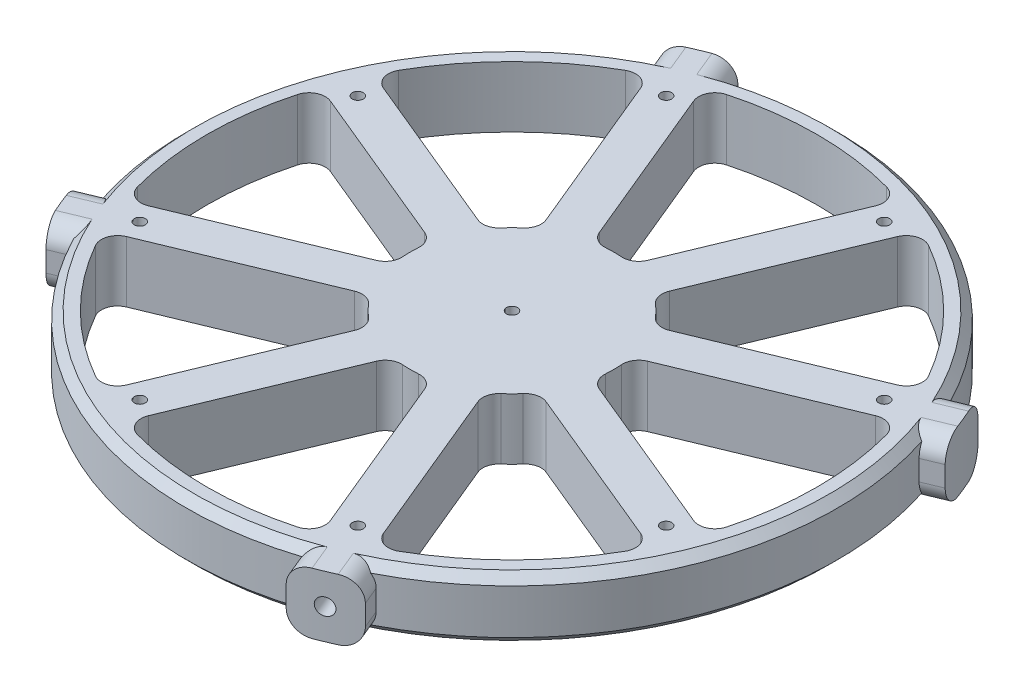
SolidWorks part; units mm, degrees
ref_plane "Front Plane" through (0, 0, 0) normal (0, 0, 1) x (1, 0, 0)
ref_plane "Top Plane" through (0, 0, 0) normal (0, 1, 0) x (1, 0, 0)
ref_plane "Right Plane" through (0, 0, 0) normal (1, 0, 0) x (0, 0, -1)
sketch "Sketch2" plane through (0, 0, 0) normal (1, 0, 0) x (0, 0, -1)
  line L0 (0, 0) -> (-79.9998, 0)
  line L1 (-79.9998, 0) -> (-79.9998, 15)
  line L2 (-79.9998, 15) -> (0, 15)
  line L5 (0, 15) -> (0, 0)
  dimension "D1" = 79.9998
  dimension "D2" = 15
ref_axis "Axis1" through (0, -0.75, 0) along (0, 1, 0)
revolve "Revolve1" add sketch "Sketch2" angle 360 about axis through (0, -0.75, 0) along (0, 1, 0)
hole_wizard "#6-32 Tapped Hole2" positions "Sketch6" profile "Sketch7" tap size "#6-32" standard "ANSI Inch" end condition through all
sketch "Sketch6" plane through (0, 15, 0) normal (0, 1, 0) x (1, 0, 0)
  line L0 (0, 0) -> (-53.438, 129.0108) construction
  line L2 (0, 0) -> (0, 109.0908) construction
  point P0 (-26.7878, 64.6716)
  dimension "D1" = 22.5
  dimension "D2" = 70
sketch "Sketch7" plane through (-26.7878, 15, -64.6716) normal (1, 0, 0) x (0, 0, 1)
  line L0 (0, 0) -> (0, 15)
  line L1 (0, 15) -> (1.3525, 15)
  line L2 (1.3525, 15) -> (1.3525, 0)
  line L5 (1.3525, 0) -> (0, 0)
  line L11 (0, -6.35) -> (0, 107.95) construction
  dimension "Thread Major Dia." = 2.7051
  dimension "Thru Tap Drill Depth" = 15
pattern_circular "CirPattern3" count 8 over 360 about axis through (0, -0.75, 0) along (0, 1, 0) of "#6-32 Tapped Hole2"
sketch "Sketch8" plane through (0, 15, 0) normal (0, 1, 0) x (1, 0, 0)
  line L4 (0, 0) -> (0, 93.9995) construction
  line L5 (0, 0) -> (113.8372, 0) construction
  line L6 (-4.7544, 24.5438) -> (-24.0179, 71.0501)
  line L7 (4.7544, 24.5438) -> (24.0179, 71.0501)
  line L8 (0, 0) -> (-26.7878, 64.6716) construction
  arc A0 (-4.7544, 24.5438) -> (4.7544, 24.5438) centre (0, 0) cw
  arc A1 (-24.0179, 71.0501) -> (24.0179, 71.0501) centre (0, 0) cw
  circle A2 centre (0, 0) radius 79.9998 construction
  dimension "D1" = 25
  dimension "D2" = 5
  dimension "D3" = 5
extrude "Cut-Extrude1" cut sketch "Sketch8" against normal through all
fillet "Fillet1" radius 4 4 edges at (4.7544, 7.5, -24.5438) (24.0179, 7.5, -71.0501) (-4.7544, 7.5, -24.5438) (-24.0179, 7.5, -71.0501)
pattern_circular "CirPattern4" count 8 over 360 about axis through (0, -0.75, 0) along (0, 1, 0) of "Cut-Extrude1", "Fillet1"
hole_wizard "#6-32 Tapped Hole1" positions "Sketch9" profile "Sketch11" tap size "#6-32" standard "ANSI Inch" end condition through all
sketch "Sketch9" plane through (0, 0, 0) normal (0, -1, 0) x (-1, 0, 0)
  point P0 (0, 0)
sketch "Sketch11" plane through (0, 0, 0) normal (1, 0, 0) x (0, 0, -1)
  line L0 (0, 0) -> (0, 15)
  line L1 (0, 15) -> (1.3525, 15)
  line L2 (1.3525, 15) -> (1.3525, 0)
  line L5 (1.3525, 0) -> (0, 0)
  line L11 (0, -6.35) -> (0, 107.95) construction
  dimension "Thru Tap Drill Dia." = 2.7051
  dimension "Thru Tap Drill Depth" = 15
cosmetic thread "Hole Thread1" parameters "D2"=3.5052
sketch "Sketch12" plane through (0, 15, 0) normal (0, 1, 0) x (1, 0, 0)
  line L0 (0, 0) -> (-26.7878, 64.6716) construction
  line L1 (-23.5987, 76.44) -> (-25.4738, 80.967)
  line L2 (-39.2396, 75.265) -> (-37.3645, 70.738)
  circle A0 centre (0, 0) radius 79.9998 construction
  arc A1 (-25.4738, 80.967) -> (-39.2396, 75.265) centre (0, 0) ccw
  circle A2 centre (0, 0) radius 79.9998 construction
  arc A3 (-37.3645, 70.738) -> (-23.5987, 76.44) centre (0, 0) cw
  point P12 (0, 0)
  dimension "D1" = 14.9
  dimension "D2" = 4.9
extrude "Boss-Extrude1" add sketch "Sketch12" against normal blind 15
fillet "Fillet2" radius 5 4 edges at (-24.5362, 15, -78.7035) (-38.302, 15, -73.0015) (-24.5362, 0, -78.7035) (-38.302, 0, -73.0015)
pattern_circular "CirPattern5" count 4 over 360 about axis through (0, -0.75, 0) along (0, 1, 0) of "Fillet2", "Boss-Extrude1"
chamfer "Chamfer1" distance 2 angle 45 8 edges at (73.9102, 0, 30.6146) (-30.6146, 0, 73.9102) (-73.9102, 0, -30.6146) (-73.9102, 15, -30.6146) (-30.6146, 15, 73.9102) (73.9102, 15, 30.6146) (30.6146, 0, -73.9102) (30.6146, 15, -73.9102)
ref_plane "Plane1" through (0, 0, 0) normal (0.3827, 0, 0.9239) x (0, 1, 0)
hole_wizard "#20 (0.161) Diameter Hole1" positions "Sketch16" profile "Sketch15" hole size "#20" standard "ANSI Inch" end condition through all
sketch "Sketch16" plane through (0, 0, 0) normal (0.3827, 0, 0.9239) x (0, 1, 0)
  point P0 (7.5, 0)
  dimension "D1" = 7.5
sketch "Sketch15" plane through (0, 7.5, 0) normal (0, 1, 0) x (-0.9239, 0, 0.3827)
  line L0 (0, 0) -> (0, 106.1589)
  line L1 (0, 106.1589) -> (2.0447, 106.1589)
  line L2 (2.0447, 106.1589) -> (2.0447, 0)
  line L5 (2.0447, 0) -> (0, 0)
  line L11 (0, -6.35) -> (0, 107.95) construction
  dimension "Thru Hole Dia." = 4.0894
  dimension "Thru Hole Depth" = 106.1589
